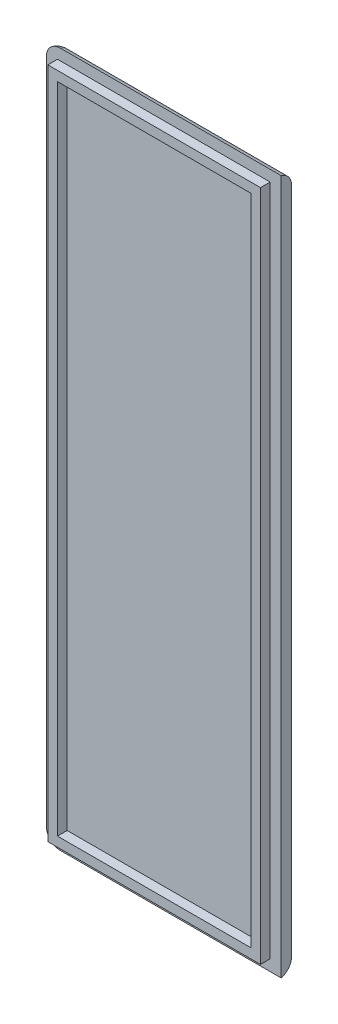
SolidWorks part; units mm, degrees
ref_plane "Plan de face" through (0, 0, 0) normal (0, 0, 1) x (1, 0, 0)
ref_plane "Plan de dessus" through (0, 0, 0) normal (0, 1, 0) x (1, 0, 0)
ref_plane "Plan de droite" through (0, 0, 0) normal (1, 0, 0) x (0, 0, -1)
sketch "Esquisse1" plane through (0, 0, 0) normal (0, 0, 1) x (1, 0, 0)
  line L1 (0, 0) -> (34, 0)
  line L2 (0, 0) -> (0, 100.65)
  line L3 (0, 100.65) -> (34, 100.65)
  line L4 (34, 0) -> (34, 100.65)
  dimension "D1" = 34
  dimension "D2" = 100.65
extrude "Boss.-Extru.1" add sketch "Esquisse1" along normal blind 1.5
sketch "Esquisse2" plane through (0, 0, 1.5) normal (0, 0, 1) x (1, 0, 0)
  line L0 (0, 0) -> (34, 0) construction
  line L1 (1.6, 99.05) -> (32.4, 99.05)
  line L2 (1.6, 99.05) -> (1.6, 1.6)
  line L3 (1.6, 1.6) -> (32.4, 1.6)
  line L4 (32.4, 99.05) -> (32.4, 1.6)
  line L5 (0, 100.65) -> (0, 0) construction
  line L6 (34, 0) -> (34, 100.65) construction
  line L7 (34, 100.65) -> (0, 100.65) construction
  line L9 (3, 97.65) -> (31, 97.65)
  line L10 (3, 97.65) -> (3, 3)
  line L11 (3, 3) -> (31, 3)
  line L12 (31, 97.65) -> (31, 3)
  point P16 (2.9, 97.75)
  dimension "D1" = 1.6
  dimension "D2" = 1.6
  dimension "D3" = 1.6
  dimension "D4" = 1.6
  dimension "D5" = 1.4
  dimension "D6" = 1.4
  dimension "D7" = 1.4
  dimension "D8" = 1.4
extrude "Boss.-Extru.2" add sketch "Esquisse2" along normal blind 1.4
fillet "Congé6" radius 2 1 edges at (0, 0, 0.75)
fillet "Congé8" radius 2 1 edges at (0, 100.65, 0.75)
fillet "Congé9" radius 2 5 edges at (18, 100.65, 0) (0.5858, 100.0642, 0) (0, 50.325, 0) (0.5858, 0.5858, 0) (18, 0, 0)
